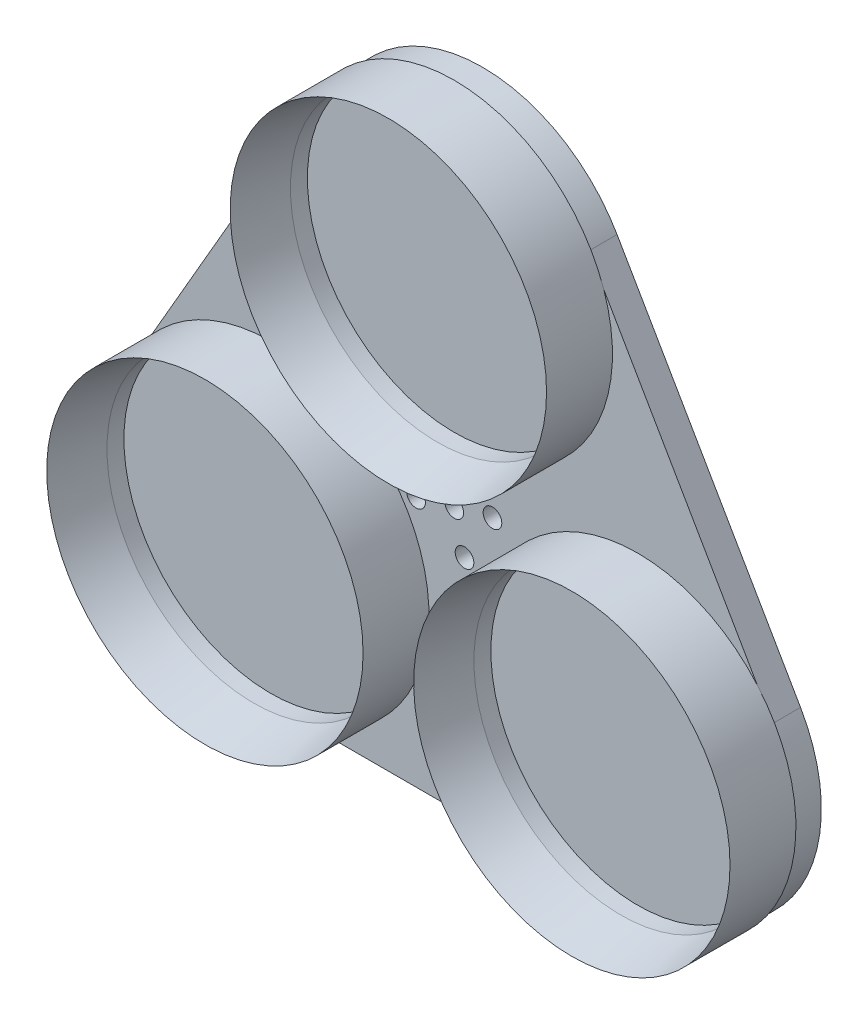
SolidWorks part; units mm, degrees
ref_plane "前视基准面" through (0, 0, 0) normal (0, 0, 1) x (1, 0, 0)
ref_plane "上视基准面" through (0, 0, 0) normal (0, 1, 0) x (1, 0, 0)
ref_plane "右视基准面" through (0, 0, 0) normal (1, 0, 0) x (0, 0, -1)
other "Configuration Table"
sketch "草图1" plane through (0, 0, 0) normal (0, 0, 1) x (1, 0, 0)
  line L0 (0, 0) -> (0, 37.5) construction
  line L1 (0, 0) -> (-32.476, -18.75) construction
  line L2 (0, 0) -> (32.476, -18.75) construction
  line L3 (-23.8157, 51.25) -> (-56.2917, -5)
  line L4 (-32.476, -46.25) -> (32.476, -46.25)
  line L5 (56.2917, -5) -> (23.8157, 51.25)
  line L6 (0, 0) -> (-40.0537, 23.125) construction
  circle A2 centre (0, 0) radius 37.5 construction
  circle A3 centre (0, 37.5) radius 26.5 construction
  circle A4 centre (32.476, -18.75) radius 26.5 construction
  circle A5 centre (-32.476, -18.75) radius 26.5 construction
  arc A6 (-56.2917, -5) -> (-32.476, -46.25) centre (-32.476, -18.75) ccw
  arc A7 (32.476, -46.25) -> (56.2917, -5) centre (32.476, -18.75) ccw
  arc A8 (23.8157, 51.25) -> (-23.8157, 51.25) centre (0, 37.5) ccw
  dimension "D3" = 53
  dimension "D4" = 75
  dimension "D5" = 55
  dimension "D1" = 60
extrude "凸台-拉伸1" add sketch "草图1" along normal blind 5
sketch "草图2" plane through (0, 0, 5) normal (0, 0, 1) x (1, 0, 0)
  circle A0 centre (-32.476, -18.75) radius 26
  circle A1 centre (0, 37.5) radius 26
  circle A2 centre (32.476, -18.75) radius 26
  circle A3 centre (0, 37.5) radius 28
  circle A4 centre (32.476, -18.75) radius 28
  circle A5 centre (-32.476, -18.75) radius 28
  dimension "D1" = 52
  dimension "D2" = 56
extrude "凸台-拉伸2" add sketch "草图2" along normal blind 16
sketch "草图3" plane through (0, 0, 5) normal (0, 0, 1) x (1, 0, 0)
  line L0 (-1.8117, 6.7615) -> (1.8117, -6.7615) construction
  line L1 (-6.7615, -1.8117) -> (6.7615, 1.8117) construction
  line L2 (0, 0) -> (7, 0) construction
  circle A0 centre (0, 0) radius 7 construction
  circle A1 centre (0, 0) radius 1.65
  circle A2 centre (-1.8117, 6.7615) radius 1.65
  circle A3 centre (6.7615, 1.8117) radius 1.65
  circle A4 centre (1.8117, -6.7615) radius 1.65
  circle A5 centre (-6.7615, -1.8117) radius 1.65
  dimension "D1" = 14
  dimension "D2" = 3.3
  dimension "D3" = 90
  dimension "D4" = 15
extrude "切除-拉伸1" cut sketch "草图3" against normal through all
chamfer "倒角1" distance 3 distance2 13 3 edges at (-6.476, -18.75, 21) (58.476, -18.75, 21) (26, 37.5, 21) first distance on face at (-4.476, -18.75, 21) first distance on face at (60.476, -18.75, 21) first distance on face at (28, 37.5, 21)
sketch "草图4" plane through (0, 0, 5) normal (0, 0, 1) x (1, 0, 0)
  circle A0 centre (-1.8117, 6.7615) radius 2.6
  circle A1 centre (-6.7615, -1.8117) radius 2.6
  circle A2 centre (0, 0) radius 2.6
  circle A3 centre (1.8117, -6.7615) radius 2.6
  circle A4 centre (6.7615, 1.8117) radius 2.6
  dimension "D1" = 5.2
